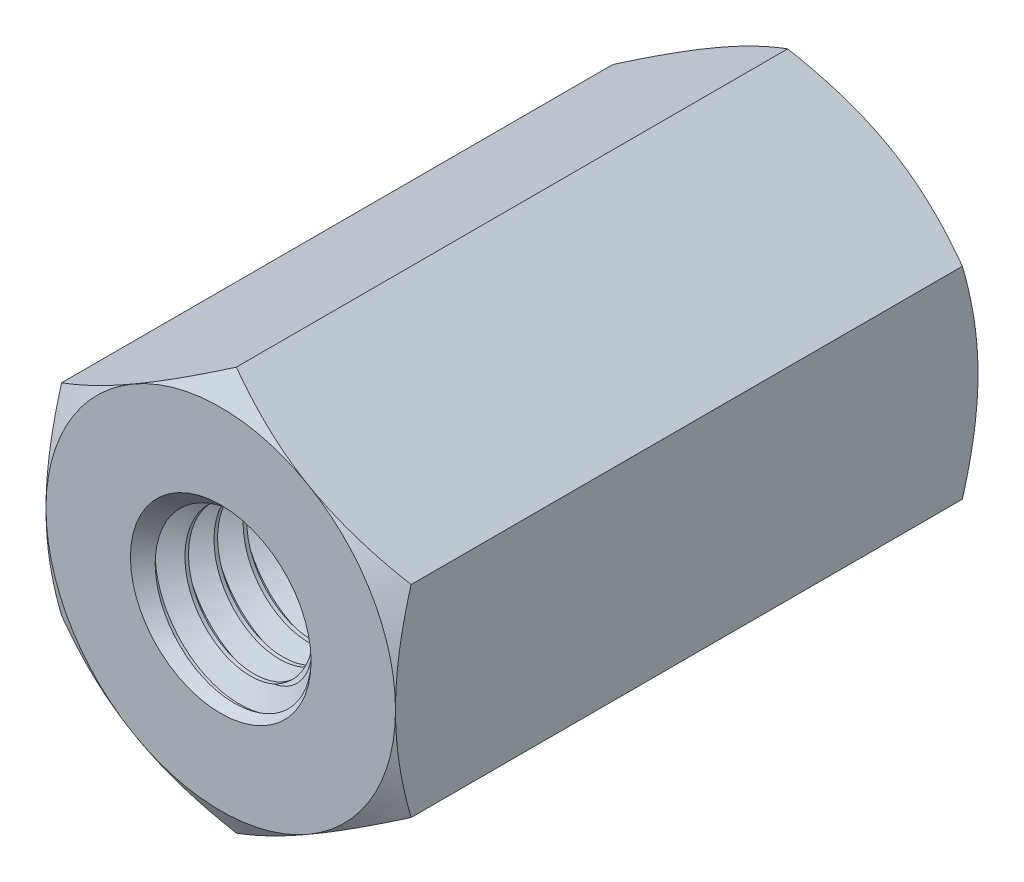
SolidWorks part; units mm, degrees
ref_plane "Front Plane" through (0, 0, 0) normal (0, 0, 1) x (1, 0, 0)
ref_plane "Top Plane" through (0, 0, 0) normal (0, 1, 0) x (1, 0, 0)
ref_plane "Right Plane" through (0, 0, 0) normal (1, 0, 0) x (0, 0, -1)
sketch "Sketch3" plane through (0, 0, 0) normal (1, 0, 0) x (0, 0, -1)
  line L0 (-5, 0) -> (5, 0) construction
  line L1 (0, 3) -> (0, -3) construction
  line L2 (-5, 1.5) -> (-5, -1.5) construction
  point P2 (0.2, 0)
  point P3 (-0.2, 0)
  dimension "D1" = 4.8
  dimension "Length" = 10
  dimension "Min Thread Length" = 4.8
  dimension "Thread Dia" = 3
  dimension "Hex" = 6
sketch "Sketch1" plane through (0, 0, 0) normal (0, 0, 1) x (1, 0, 0)
  line L1 (0, 3.4641) -> (-3, 1.7321)
  line L2 (-3, 1.7321) -> (-3, -1.7321)
  line L3 (-3, -1.7321) -> (0, -3.4641)
  line L4 (0, -3.4641) -> (3, -1.7321)
  line L5 (3, -1.7321) -> (3, 1.7321)
  line L6 (3, 1.7321) -> (0, 3.4641)
  circle A0 centre (0, 0) radius 3 construction
  circle A1 centre (0, 0) radius 1.5
extrude "Extrude1" add sketch "Sketch1" along normal up to vertex (5 mm away) and the other way up to vertex (5 mm away) up to point (0, 0, 5) other way up to point (0, 0, -5)
sketch "Sketch11" plane through (0, 0, -5) normal (0, 0, -1) x (-1, 0, 0)
  circle A0 centre (0, 0) radius 1.5 construction
  circle A1 centre (0, 0) radius 1.5
curve "Helix/Spiral1" pitch 0.5 height 10.5 radius 1.5 centre (0, 0, -5) axis (0, 0, 1) start towards (0, 1, 0) parameters "Pitch"=0.5
sketch "Sketch12" plane through (0, 0, 0) normal (1, 0, 0) x (0, 0, -1)
  line L0 (5.4375, 1.5) -> (5, 1.5)
  line L1 (5.4375, 1.5) -> (5.25, 1.1752)
  line L2 (5.25, 1.1752) -> (5.1875, 1.1752)
  line L3 (5.1875, 1.1752) -> (5, 1.5)
  line L4 (5.2187, 1.1752) -> (5.2187, 1.5) construction
  line L5 (5.3437, 1.3376) -> (5.0937, 1.3376) construction
  dimension "D1" = 0.0625
  dimension "D2" = 0.25
  dimension "D3" = 60
sweep "Sweep1" add profiles "Sketch12" path "Helix/Spiral1"
sketch "Sketch6" plane through (0, 0, -5) normal (0, 0, -1) x (-1, 0, 0)
  line L6 (0, 3.4641) -> (-3, 1.7321)
  line L7 (-3, 1.7321) -> (-3, -1.7321)
  line L8 (-3, -1.7321) -> (0, -3.4641)
  line L9 (0, -3.4641) -> (3, -1.7321)
  line L10 (3, -1.7321) -> (3, 1.7321)
  line L11 (3, 1.7321) -> (0, 3.4641)
  line L12 (0, 3.4641) -> (-3, 1.7321)
  line L13 (-3, 1.7321) -> (-3, -1.7321)
  line L14 (-3, -1.7321) -> (0, -3.4641)
  line L15 (0, -3.4641) -> (3, -1.7321)
  line L16 (3, -1.7321) -> (3, 1.7321)
  line L17 (3, 1.7321) -> (0, 3.4641)
  dimension "D1" = 0
extrude "Extrude2" cut sketch "Sketch6" along normal through all
sketch "Sketch7" plane through (0, 0, -5) normal (0, 0, -1) x (-1, 0, 0)
  circle A2 centre (0, 0) radius 1.5508
  circle A3 centre (0, 0) radius 1.5508
  dimension "D1" = 0.0508
extrude "Extrude3" cut sketch "Sketch7" against normal through all draft 43
sketch "Sketch8" plane through (0, 0, -5) normal (0, 0, -1) x (-1, 0, 0)
  circle A0 centre (0, 0) radius 3 construction
  circle A1 centre (0, 0) radius 3
extrude "Extrude4" cut sketch "Sketch8" against normal through all draft 60 flip side to cut
mirror "Mirror1" about plane through (0, 0, 0) normal (0, 0, 1) of "Extrude2", "Extrude3", "Extrude4"
sketch "Sketch9" [suppressed] plane through (0, 0, 0) normal (1, 0, 0) x (0, 0, -1)
  line L1 (-1.2, 1.1353) -> (1.2, 1.1353)
  line L2 (-1.2, 1.1353) -> (-1.2, 0)
  line L3 (-1.2, 0) -> (1.2, 0)
  line L4 (1.2, 1.1353) -> (1.2, 0)
  line L7 (-6, 0) -> (6, 0) construction
revolve "Revolve" [suppressed] add sketch "Sketch9" angle 360 about L0
sketch "Sketch10" [suppressed] plane through (0, 0, 0) normal (1, 0, 0) x (0, 0, -1)
  line L0 (6, 1.25) -> (1.2, 1.25)
  line L1 (-6, 1.25) -> (-1.2, 1.25)
  line L2 (1.2, 1.25) -> (1.2, -1.25)
  line L3 (-6, -1.25) -> (-1.2, -1.25)
  line L4 (-1.2, 1.25) -> (-1.2, -1.25)
  line L5 (1.2, -1.25) -> (6, -1.25)
equation "\"D1@Sketch3\" = \"Min Thread Length@Sketch3\""
equation "\"D3@Helix/Spiral1\" = \"Length@Sketch3\"+\"Pitch@Helix/Spiral1\""
equation "\"D1@Sketch12\" = \"Pitch@Helix/Spiral1\"*.125"
equation "\"D2@Sketch12\" = \"Pitch@Helix/Spiral1\"*.5"
